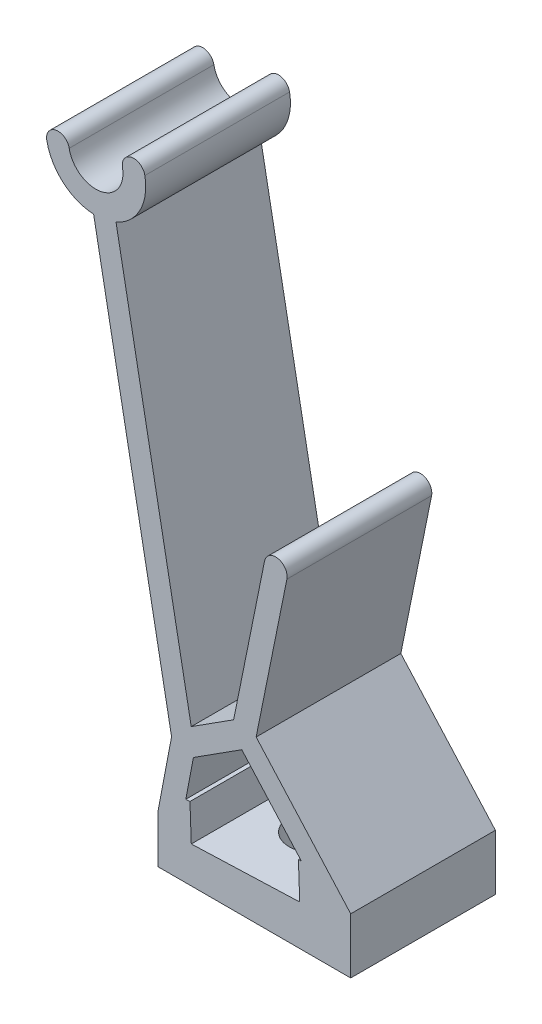
SolidWorks part; units mm, degrees
ref_plane "Front Plane" through (0, 0, 0) normal (0, 0, 1) x (1, 0, 0)
ref_plane "Top Plane" through (0, 0, 0) normal (0, 1, 0) x (1, 0, 0)
ref_plane "Right Plane" through (0, 0, 0) normal (1, 0, 0) x (0, 0, -1)
sketch "sketch - skeleton" plane through (0, 0, 0) normal (0, 0, 1) x (1, 0, 0)
  line L0 (0, 0) -> (0, -50000) construction
  line L1 (0, 0) -> (7.455, 0.2734) construction
  line L2 (9.9233, 0.3639) -> (10.6101, 4.558) construction
  line L3 (10.6101, 4.558) -> (7.9471, 2.8569) construction
  line L4 (7.9471, 2.8569) -> (7.455, 0.2734) construction
  line L5 (10.6101, 4.558) -> (12.0093, 11.478) construction
  line L6 (7.9471, 2.8569) -> (4.1146, 23.199) construction
  line L7 (7.455, 0.2734) -> (9.9233, 0.3639) construction
  line L8 (9.9233, 0.3639) -> (14.65, 0.5372) construction
  line L9 (10.6101, 4.558) -> (13.9821, 6.712) construction
  line L11 (7.9471, 2.8569) -> (5.8206, 1.4986) construction
  dimension "D1" = 92.1
  dimension "D2" = 7.46
  dimension "D3" = 2.47
  dimension "D4" = 4.25
  dimension "D5" = 78.6
  dimension "D6" = 3.16
  dimension "D7" = 7.06
  dimension "D8" = 20.7
  dimension "D10" = 46
  dimension "D11" = 111.9
  dimension "D9" = 2.63
sketch "Sketch1" plane through (0, 0, 0) normal (0, 0, 1) x (1, 0, 0)
  line L0 (8.3979, 2.5516) -> (8.0635, 0.796)
  line L1 (7.4382, 2.8574) -> (6.8464, -0.2493)
  line L2 (8.0635, 0.796) -> (9.496, 0.8485)
  line L3 (10.3506, -0.1208) -> (6.8464, -0.2493) construction
  line L4 (7.9471, 2.8569) -> (7.455, 0.2734) construction
  line L5 (11.5192, 11.5771) -> (10.1621, 4.8651)
  line L6 (7.455, 0.2734) -> (9.9233, 0.3639) construction
  line L7 (10.3506, -0.1208) -> (15.3002, 0.0607) construction
  line L8 (9.9358, 3.5339) -> (8.3979, 2.5516)
  line L9 (10.6101, 4.558) -> (7.9471, 2.8569) construction
  line L10 (9.0969, 0.8339) -> (9.1335, -0.1654) construction
  line L11 (7.2099, 1.6587) -> (8.1922, 1.4716) construction
  line L12 (8.9779, 4.1086) -> (9.5162, 3.2659) construction
  line L15 (9.9233, 0.3639) -> (10.6101, 4.558) construction
  line L16 (9.8006, 2.7086) -> (10.7875, 2.547) construction
  line L17 (12.4994, 11.3789) -> (11.1499, 4.7044)
  line L18 (10.6101, 4.558) -> (12.0093, 11.478) construction
  line L19 (10.5977, 7.0192) -> (11.5778, 6.821) construction
  line L20 (4.0182, 21.0106) -> (7.4382, 2.8574)
  line L21 (8.3015, 3.6766) -> (5.0009, 21.1957)
  line L22 (7.9471, 2.8569) -> (4.1146, 23.199) construction
  line L23 (6.0985, 9.9681) -> (7.0813, 10.1533) construction
  line L24 (8.3015, 3.6766) -> (10.1621, 4.8651)
  line L25 (10.5155, 0.8859) -> (13.1356, 0.982)
  line L26 (10.6101, 4.558) -> (14.2179, 0.5213) construction
  line L27 (-199855.7554, -7328.3779) -> (199880.3288, 7329.2789) construction
  line L28 (11.1499, 4.7044) -> (15.3002, 0.0607)
  line L29 (13.1356, 0.982) -> (10.9345, 3.4448)
  line L30 (12.4991, 1.6942) -> (13.2447, 2.3606) construction
  line L32 (9.496, 0.8485) -> (10.5155, 0.8859)
  line L33 (9.9358, 3.5339) -> (10.5208, 3.9076)
  line L34 (6.8464, -0.2493) -> (6.8464, -2.379)
  line L35 (10.9345, 3.4448) -> (10.5208, 3.9076)
  line L36 (6.8464, -2.379) -> (15.3002, -2.379)
  line L37 (15.3002, -2.379) -> (15.3002, 0.0607)
  line L38 (1.9619, 22.7935) -> (6.2674, 23.6046) construction
  arc A0 (11.5192, 11.5771) -> (12.4994, 11.3789) centre (12.0093, 11.478) cw
  arc A2 (2.9446, 22.9786) -> (5.2847, 23.4195) centre (4.1146, 23.199) ccw
  arc A3 (5.0009, 21.1957) -> (6.2674, 23.6046) centre (4.1146, 23.199) ccw
  arc A4 (1.9619, 22.7935) -> (2.9446, 22.9786) centre (2.4533, 22.886) cw
  arc A5 (6.2674, 23.6046) -> (5.2847, 23.4195) centre (5.776, 23.512) ccw
  arc A6 (1.9619, 22.7935) -> (4.0182, 21.0106) centre (4.1146, 23.199) ccw
  point P25 (9.247, 3.6873)
  point P27 (7.701, 1.5651)
  point P28 (9.1152, 0.3342)
  point P36 (10.2941, 2.6278)
  point P38 (11.0877, 6.9201)
  point P51 (6.5899, 10.0607)
  point P61 (12.8719, 2.0274)
  dimension "D3" = 2.3812
  dimension "D4" = 4.3812
  dimension "D1" = 1
  dimension "D2" = 3.175
extrude "Boss-Extrude1" add sketch "Sketch1" along normal blind 6.35
sketch "Sketch2" plane through (-0.0183, 0.4997, 0) normal (-0.0366, 0.9993, 0) x (0.9993, 0.0366, 0)
  line L0 (-199990.07, 0) -> (200014.6599, 0) construction
  line L1 (8.2693, 0) -> (13.0318, 0)
  line L2 (8.2693, 0) -> (8.2693, -6.35)
  line L3 (8.2693, -6.35) -> (13.0318, -6.35)
  line L4 (13.0318, 0) -> (13.0318, -6.35)
  line L6 (8.0873, -6.35) -> (13.1628, -6.35) construction
  dimension "D1" = 4.7625
extrude "Cut-Extrude1" cut sketch "Sketch2" against normal blind 1.5875
hole_wizard "#2 Clearance Hole1" positions "Sketch4" profile "Sketch3" hole size "#2" standard "ANSI Inch" end condition up to next
sketch "Sketch4" plane through (0, -2.379, 0) normal (0, -1, 0) x (-1, 0, 0)
  line L0 (-13.0629, -6.35) -> (-13.0629, 0) construction
  line L1 (-13.0629, -6.35) -> (-13.0629, 0) construction
  line L2 (-8.3036, 0) -> (-8.3036, -6.35) construction
  line L3 (-8.3036, 0) -> (-8.3036, -6.35) construction
  line L4 (-13.0629, -3.175) -> (-8.3036, -3.175) construction
  point P0 (-10.6833, -3.175)
sketch "Sketch3" plane through (10.6833, -2.379, 3.175) normal (1, 0, 0) x (0, 0, -1)
  line L0 (0, 0) -> (0, 1.6825)
  line L1 (0, 1.6825) -> (1.2192, 1.6825)
  line L2 (1.2192, 1.6825) -> (1.2192, 0)
  line L5 (1.2192, 0) -> (0, 0)
  line L11 (0, -6.35) -> (0, 107.95) construction
  dimension "Thru Hole Dia." = 2.4384
  dimension "Thru Hole Depth" = 1.6825
equation "\"axle-diameter\"=2"
equation "\"switch-thickness\"=12"
equation "\"base-width\"=4.0"
equation "\"axle-bushing-radius\"=3"
equation "\"clearance\"= 0.25"
equation "\"arm-width\"=1.0"
equation "\"min-diameter\"=70"
equation "\"alpha\"=92.1"
equation "\"beta\"=26.0"
equation "\"gamma\"=78.6"
equation "\"delta\"=111.9"
equation "\"epsilon\"=46.0"
equation "\"eta\"=-228.1"
equation "\"l_AB\"=2.47"
equation "\"l_AC\"=2.63"
equation "\"l_BD\"=4.25"
equation "\"l_CD\"=3.16"
equation "\"l_CE\"=20.70"
equation "\"l_DF\"=7.06"
equation "\"l_OA\"=7.46"
equation "\"D1@sketch - skeleton\"=\"alpha\""
equation "\"D2@sketch - skeleton\"=\"l_OA\""
equation "\"D3@sketch - skeleton\"=\"l_AB\""
equation "\"D4@sketch - skeleton\"=\"l_BD\""
equation "\"D5@sketch - skeleton\"=\"gamma\""
equation "\"D6@sketch - skeleton\"=\"l_CD\""
equation "\"D7@sketch - skeleton\"=\"l_DF\""
equation "\"D8@sketch - skeleton\"=\"l_CE\""
equation "\"D10@sketch - skeleton\"=\"epsilon\""
equation "\"D11@sketch - skeleton\"=\"delta\""
equation "\"D9@sketch - skeleton\"=\"l_AC\""
equation "\"D_groove\"=2.3812"
equation "\"D3@Sketch1\"=\"D_groove\""
equation "\"D4@Sketch1\"=\"D_groove\"+2*\"arm-width\""
